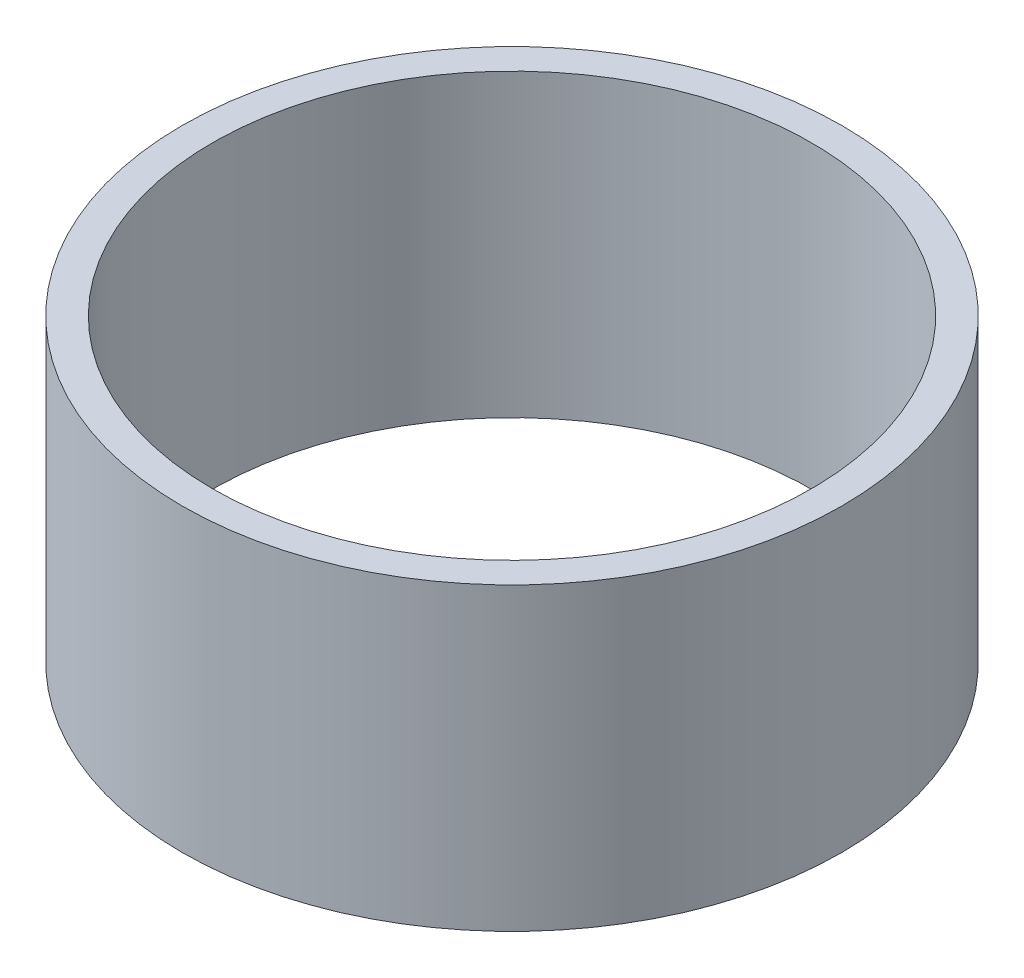
SolidWorks part; units mm, degrees
ref_plane "Front Plane" through (0, 0, 0) normal (0, 0, 1) x (1, 0, 0)
ref_plane "Top Plane" through (0, 0, 0) normal (0, 1, 0) x (1, 0, 0)
ref_plane "Right Plane" through (0, 0, 0) normal (1, 0, 0) x (0, 0, -1)
sketch "Sketch1" plane through (0, 0, 0) normal (0, 1, 0) x (1, 0, 0)
  circle A0 centre (0, 0) radius 57.5
  dimension "SLEEVE_OD" = 115
extrude "Boss-Extrude1" add sketch "Sketch1" along normal blind 52.3355
sketch "Sketch2" plane through (0, 0, 0) normal (0, 1, 0) x (1, 0, 0)
  circle A0 centre (0, 0) radius 52.2476
  dimension "BORE_D" = 104.4953
extrude "Cut-Extrude1" cut sketch "Sketch2" along normal through all
chamfer "Chamfer1" distance 2.9179 angle 45 rebuild error yes
